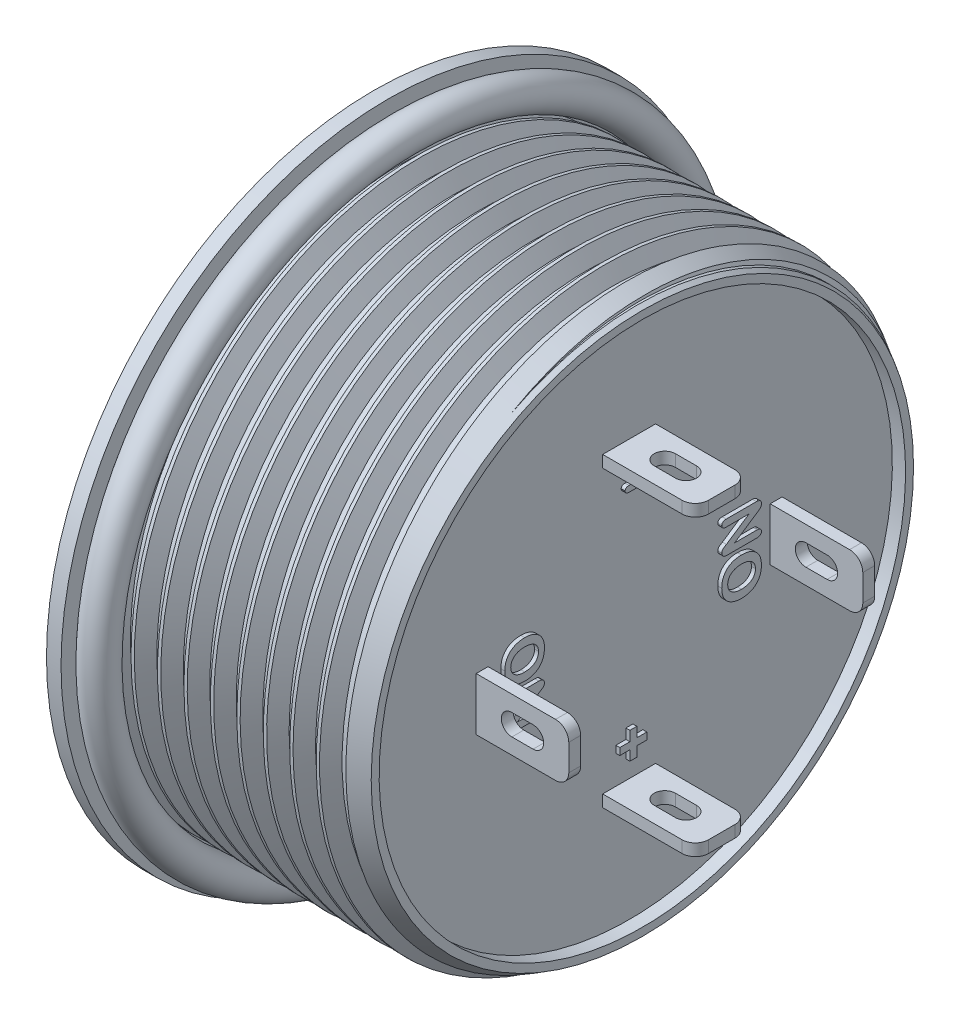
SolidWorks part; units mm, degrees
ref_plane "Front Plane" through (0, 0, 0) normal (0, 0, 1) x (1, 0, 0)
ref_plane "Top Plane" through (0, 0, 0) normal (0, 1, 0) x (1, 0, 0)
ref_plane "Right Plane" through (0, 0, 0) normal (1, 0, 0) x (0, 0, -1)
sketch "Sketch1" plane through (0, 0, 0) normal (0, 0, 1) x (1, 0, 0)
  line L0 (9.1, 0) -> (-2.7412, 0) construction
  line L1 (-1.8, 9) -> (-1.8, 10)
  line L2 (9.1, 0) -> (-1.8, 0)
  line L3 (9.6, 9.95) -> (9.6, 10.35)
  line L4 (0, 12.375) -> (-0.55, 12.375)
  line L5 (-1.8, 0) -> (-1.8, 7.7)
  line L6 (-1.8, 9) -> (-1.7, 9)
  line L8 (-1.8, 7.7) -> (-1.7, 7.7)
  line L9 (-1.7, 9) -> (-1.7, 7.7)
  line L10 (-1.8, 10) -> (-0.55, 12.375)
  line L13 (0, 12.375) -> (0, 10.35)
  line L14 (0, 10.35) -> (9.6, 10.35)
  line L16 (9.6, 9.95) -> (9.1, 9.95)
  line L19 (9.1, 9.95) -> (9.1, 0)
  point P0 (9.6, 10.15)
  point P14 (-1.75, 9)
  dimension "D1" = 24.75
  dimension "H1" = 1.8
  dimension "HS" = 0.1
  dimension "D2" = 20.7
  dimension "D3" = 20
  dimension "D4" = 15.4
  dimension "D5" = 18
  dimension "D6" = 0.5
  dimension "H2" = 9.6
  dimension "D7" = 0.4
  dimension "H4" = 0.55
revolve "Revolve1" add sketch "Sketch1" angle 360 about L0
thread "Thread1" pitch 1 method extrude profile "Thread Profile1" start angle 0, offset 1, length 0, pitch 1, diameter 10.7
ref_plane "Plane1" through (10.6, 0, 10.35) normal (0, -1, 0) x (0, 0, 1)
sketch "Thread Profile1" plane through (10.6, 0, 10.35) normal (0, -1, 0) x (0, 0, 1)
  line L0 (0, 0) -> (0, 1) construction
  line L1 (0, 0) -> (0.5413, 0.3125)
  line L2 (0.5413, 0.3125) -> (0.5413, 0.4375)
  line L3 (0.5413, 0.4375) -> (0, 0.75)
  line L4 (0.5413, 0.375) -> (0, 0.375) construction
  line L11 (0, 0) -> (0, 0.75)
  point P2 (0, 0)
  dimension "Pitch" = 1
  dimension "Profile_Angle" = 60
  dimension "Profile_Land" = 0.125
  dimension "Profile_Height" = 0.5413
sketch "Sketch5" plane through (0, 0, 0) normal (0, 0, 1) x (1, 0, 0)
  line L1 (9.6, 10.25) -> (12.6, 10.25)
  line L4 (12.6, 10.25) -> (12.6, 10.8913)
  line L5 (9.6, 10.25) -> (8.4893, 10.8913)
  line L6 (8.4893, 10.8913) -> (12.6, 10.8913)
  line L7 (0, 0) -> (21.0637, 0) construction
  dimension "D1" = 3
  dimension "D2" = 30
  dimension "D3" = 0.3
revolve "Cut-Revolve1" cut sketch "Sketch5" angle 360 about L7
sketch "Sketch6" plane through (9.1, 0, 0) normal (1, 0, 0) x (0, 0, -1)
  line L0 (0, 9.95) -> (0, -9.95) construction
  line L2 (-9.95, 0) -> (9.95, 0) construction
  line L11 (-5.3318, -1) -> (-5.7818, -1)
  line L12 (-5.3318, -1) -> (-5.3318, 1)
  line L13 (-5.3318, 1) -> (-5.7818, 1)
  line L14 (-5.7818, -1) -> (-5.7818, 1)
  line L20 (-5.5568, -1) -> (-5.5568, 1) construction
  circle A0 centre (0, 0) radius 9.95 construction
  point P32 (-5.5568, 0)
  dimension "D1" = 2
  dimension "D2" = 0.45
  dimension "B" = 11.1137
extrude "Boss-Extrude1" add sketch "Sketch6" along normal blind 3.5
sketch "Sketch7" plane through (0, 0, 5.7818) normal (0, 0, 1) x (1, 0, 0)
  line L0 (12.6, 0) -> (9.1, 0) construction
  line L1 (12.6, 1) -> (12.6, -1) construction
  line L2 (9.1, 1) -> (9.1, -1) construction
  line L3 (11.25, 0) -> (10.45, 0) construction
  line L4 (11.25, -0.4) -> (10.45, -0.4)
  line L5 (11.25, 0.4) -> (10.45, 0.4)
  line L6 (12.6, 1) -> (9.1, 1) construction
  line L7 (12.6, 0.5) -> (12.6, 1)
  line L8 (12.6, 1) -> (12.1, 1)
  line L9 (12.6, -0.5) -> (12.6, -1)
  line L10 (12.6, -1) -> (12.1, -1)
  arc A0 (11.25, -0.4) -> (11.25, 0.4) centre (11.25, 0) ccw
  arc A1 (10.45, 0.4) -> (10.45, -0.4) centre (10.45, 0) ccw
  arc A2 (12.6, 0.5) -> (12.1, 1) centre (12.1, 0.5) ccw
  arc A3 (12.1, -1) -> (12.6, -0.5) centre (12.1, -0.5) ccw
  point P8 (10.85, 0)
  dimension "D3" = 0.5
  dimension "D1" = 0.8
  dimension "D2" = 0.8
extrude "Cut-Extrude1" cut sketch "Sketch7" against normal up to next
pattern_circular "CirPattern1" count 4 over 360 about axis through (9.1, 0, 0) along (1, 0, 0) of "Cut-Extrude1", "Boss-Extrude1"
sketch "Sketch8" plane through (9.1, 0, 0) normal (1, 0, 0) x (0, 0, -1)
  line L0 (0, 0) -> (4.8318, 0) construction
  line L1 (4.8318, -1.5) -> (4.8318, 1.5) construction
  line L2 (5.3318, 1) -> (5.3318, -1) construction
  line L3 (0, 0) -> (0, -4.8318) construction
  line L4 (1.5, -4.8318) -> (-1.5, -4.8318) construction
  line L5 (1, -5.3318) -> (-1, -5.3318) construction
  line L6 (0, 0) -> (0, 4.8318) construction
  line L7 (1.5, 4.8318) -> (-1.5, 4.8318) construction
  line L8 (0, 0) -> (-4.8318, 0) construction
  line L9 (-4.8318, -1.5) -> (-4.8318, 1.5) construction
  line L10 (-5.3318, -1) -> (-5.3318, 1) construction
  line L11 (-1, 5.3318) -> (1, 5.3318) construction
  text T0 "ON" font "Arial Rounded MT Bold" height 1.5
  text T1 "+" font "Arial Rounded MT Bold" height 1.5
  text T2 "-" font "Arial Rounded MT Bold" height 1.5
  text T3 "ON" font "Arial Rounded MT Bold" height 1.5
  dimension "D1" = 0.5
  dimension "D2" = 3
  dimension "D3" = 3
  dimension "D4" = 0.5
  dimension "D5" = 3
  dimension "D6" = 0.5
  dimension "D7" = 3
  dimension "D8" = 0.5
extrude "Boss-Extrude2" add sketch "Sketch8" along normal blind 0.15
sketch "Sketch9" plane through (0, 0, 0) normal (0, 0, 1) x (1, 0, 0)
  line L0 (0, -12.375) -> (0, 12.375) construction
  line L1 (0.6169, -12.175) -> (0.6169, -10.9413) construction
  line L2 (0, -12.375) -> (1.0144, -12.375) construction
  line L3 (0.975, -10.8913) -> (0.2353, -10.8913) construction
  circle A0 centre (0.6169, -11.5581) radius 0.6169
  spline S1 degree 2 poles (8.4893, -10.3884) (8.4495, -9.5873) (8.4125, -7.7013) (8.35, -4.5113) (8.2875, 0) (8.225, 4.5113) (8.1625, 7.7013) (8.1, 10.8913) (8.0375, 10.8913) (7.975, 10.8913) (7.9125, 7.7013) (7.85, 4.5113) (7.7875, 0) (7.725, -4.5113) (7.6625, -7.7013) (7.6, -10.8913) (7.5375, -10.8913) (7.475, -10.8913) (7.4125, -7.7013) (7.35, -4.5113) (7.2875, 0) (7.225, 4.5113) (7.1625, 7.7013) (7.1, 10.8913) (7.0375, 10.8913) (6.975, 10.8913) (6.9125, 7.7013) (6.85, 4.5113) (6.7875, 0) (6.725, -4.5113) (6.6625, -7.7013) (6.6, -10.8913) (6.5375, -10.8913) (6.475, -10.8913) (6.4125, -7.7013) (6.35, -4.5113) (6.2875, 0) (6.225, 4.5113) (6.1625, 7.7013) (6.1, 10.8913) (6.0375, 10.8913) (5.975, 10.8913) (5.9125, 7.7013) (5.85, 4.5113) (5.7875, 0) (5.725, -4.5113) (5.6625, -7.7013) (5.6, -10.8913) (5.5375, -10.8913) (5.475, -10.8913) (5.4125, -7.7013) (5.35, -4.5113) (5.2875, 0) (5.225, 4.5113) (5.1625, 7.7013) (5.1, 10.8913) (5.0375, 10.8913) (4.975, 10.8913) (4.9125, 7.7013) (4.85, 4.5113) (4.7875, 0) (4.725, -4.5113) (4.6625, -7.7013) (4.6, -10.8913) (4.5375, -10.8913) (4.475, -10.8913) (4.4125, -7.7013) (4.35, -4.5113) (4.2875, 0) (4.225, 4.5113) (4.1625, 7.7013) (4.1, 10.8913) (4.0375, 10.8913) (3.975, 10.8913) (3.9125, 7.7013) (3.85, 4.5113) (3.7875, 0) (3.725, -4.5113) (3.6625, -7.7013) (3.6, -10.8913) (3.5375, -10.8913) (3.475, -10.8913) (3.4125, -7.7013) (3.35, -4.5113) (3.2875, 0) (3.225, 4.5113) (3.1625, 7.7013) (3.1, 10.8913) (3.0375, 10.8913) (2.975, 10.8913) (2.9125, 7.7013) (2.85, 4.5113) (2.7875, 0) (2.725, -4.5113) (2.6625, -7.7013) (2.6, -10.8913) (2.5375, -10.8913) (2.475, -10.8913) (2.4125, -7.7013) (2.35, -4.5113) (2.2875, 0) (2.225, 4.5113) (2.1625, 7.7013) (2.1, 10.8913) (2.0375, 10.8913) (1.975, 10.8913) (1.9125, 7.7013) (1.85, 4.5113) (1.7875, 0) (1.725, -4.5113) (1.6625, -7.7013) (1.6, -10.8913) (1.5375, -10.8913) (1.475, -10.8913) (1.4125, -7.7013) (1.35, -4.5113) (1.2875, 0) (1.225, 4.5113) (1.1625, 7.7013) (1.1, 10.8913) (1.0375, 10.8913) (0.975, 10.8913) (0.9125, 7.7013) (0.85, 4.5113) (0.7875, 0) (0.725, -4.5113) (0.6625, -7.7013) (0.6, -10.8913) (0.5375, -10.8913) (0.475, -10.8913) (0.4125, -7.7013) (0.35, -4.5113) (0.2875, 0) (0.225, 4.5113) (0.1625, 7.7013) (0.1, 10.8913) (0.0375, 10.8913) (0.0194, 10.8913) (0, 10.5816) knots 0.16352 0.16352 0.16352 0.170455 0.170455 0.181818 0.181818 0.193182 0.193182 0.204545 0.204545 0.215909 0.215909 0.227273 0.227273 0.238636 0.238636 0.25 0.25 0.261364 0.261364 0.272727 0.272727 0.284091 0.284091 0.295455 0.295455 0.306818 0.306818 0.318182 0.318182 0.329545 0.329545 0.340909 0.340909 0.352273 0.352273 0.363636 0.363636 0.375 0.375 0.386364 0.386364 0.397727 0.397727 0.409091 0.409091 0.420455 0.420455 0.431818 0.431818 0.443182 0.443182 0.454545 0.454545 0.465909 0.465909 0.477273 0.477273 0.488636 0.488636 0.5 0.5 0.511364 0.511364 0.522727 0.522727 0.534091 0.534091 0.545455 0.545455 0.556818 0.556818 0.568182 0.568182 0.579545 0.579545 0.590909 0.590909 0.602273 0.602273 0.613636 0.613636 0.625 0.625 0.636364 0.636364 0.647727 0.647727 0.659091 0.659091 0.670455 0.670455 0.681818 0.681818 0.693182 0.693182 0.704545 0.704545 0.715909 0.715909 0.727273 0.727273 0.738636 0.738636 0.75 0.75 0.761364 0.761364 0.772727 0.772727 0.784091 0.784091 0.795455 0.795455 0.806818 0.806818 0.818182 0.818182 0.829545 0.829545 0.840909 0.840909 0.852273 0.852273 0.863636 0.863636 0.875 0.875 0.886364 0.886364 0.897727 0.897727 0.909091 0.909091 0.920455 0.920455 0.931818 0.931818 0.935301 0.935301 0.935301 weights 0.963789 0.95355 1 0.92388 1 0.92388 1 0.92388 1 0.92388 1 0.92388 1 0.92388 1 0.92388 1 0.92388 1 0.92388 1 0.92388 1 0.92388 1 0.92388 1 0.92388 1 0.92388 1 0.92388 1 0.92388 1 0.92388 1 0.92388 1 0.92388 1 0.92388 1 0.92388 1 0.92388 1 0.92388 1 0.92388 1 0.92388 1 0.92388 1 0.92388 1 0.92388 1 0.92388 1 0.92388 1 0.92388 1 0.92388 1 0.92388 1 0.92388 1 0.92388 1 0.92388 1 0.92388 1 0.92388 1 0.92388 1 0.92388 1 0.92388 1 0.92388 1 0.92388 1 0.92388 1 0.92388 1 0.92388 1 0.92388 1 0.92388 1 0.92388 1 0.92388 1 0.92388 1 0.92388 1 0.92388 1 0.92388 1 0.92388 1 0.92388 1 0.92388 1 0.92388 1 0.92388 1 0.92388 1 0.92388 1 0.92388 1 0.92388 1 0.92388 1 0.92388 1 0.92388 1 0.92388 1 0.976671 0.967642 construction
  dimension "D1" = 0.2
  dimension "D2" = 1.4837
  dimension "D3" = 0.05
revolve "Revolve2" add sketch "Sketch9" angle 360 about L2
